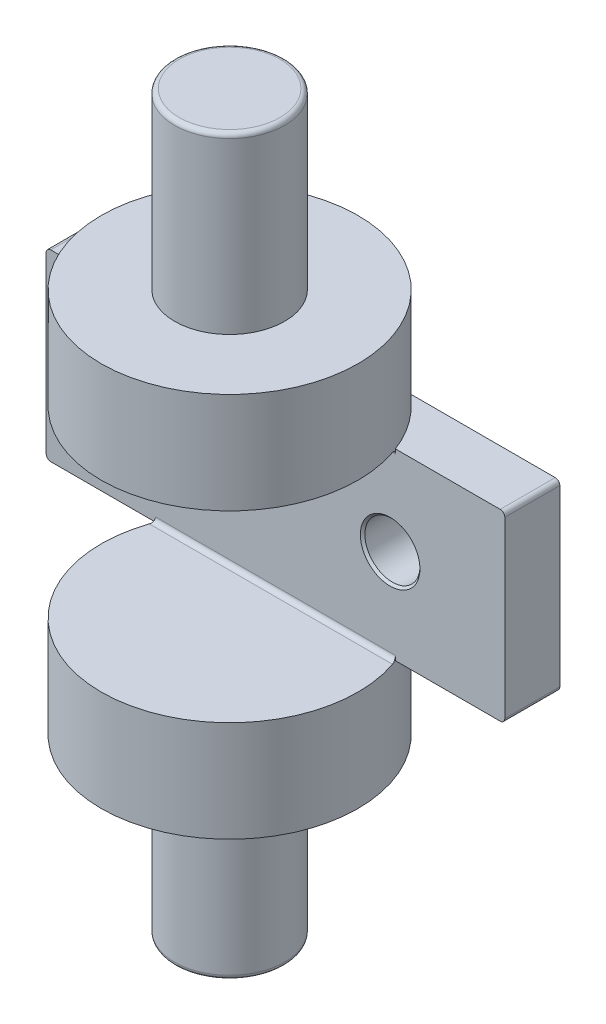
SolidWorks part; units mm, degrees
ref_plane "Alzado" through (0, 0, 0) normal (0, 0, 1) x (1, 0, 0)
ref_plane "Planta" through (0, 0, 0) normal (0, 1, 0) x (1, 0, 0)
ref_plane "Vista lateral" through (0, 0, 0) normal (1, 0, 0) x (0, 0, -1)
sketch "Croquis1" plane through (0, 0, 0) normal (0, 1, 0) x (1, 0, 0)
  circle A0 centre (0, 0) radius 6
  dimension "D1" = 12
extrude "Saliente-Extruir1" add sketch "Croquis1" against normal blind 19
sketch "Croquis2" plane through (0, 0, 0) normal (0, 1, 0) x (1, 0, 0)
  circle A0 centre (0, 0) radius 14
  dimension "D1" = 28
extrude "Saliente-Extruir2" add sketch "Croquis2" along normal blind 11
sketch "Croquis5" plane through (0, 11, 0) normal (0, 1, 0) x (1, 0, 0)
  line L0 (-25, 5) -> (25, 5)
  line L1 (-25, 5) -> (-25, 11)
  line L2 (25, 5) -> (25, 11)
  line L3 (-25, 11) -> (25, 11)
  line L4 (0, 0) -> (0, 14) construction
  point P2 (0, 5)
  dimension "D1" = 5
  dimension "D2" = 50
  dimension "D3" = 6
extrude "Saliente-Extruir6" add sketch "Croquis5" along normal blind 20
sketch "Croquis6" plane through (0, 31, 0) normal (0, 1, 0) x (1, 0, 0)
  circle A0 centre (0, 0) radius 14
extrude "Saliente-Extruir7" add sketch "Croquis6" along normal blind 11
sketch "Croquis7" plane through (0, 42, 0) normal (0, 1, 0) x (1, 0, 0)
  circle A0 centre (0, 0) radius 6
extrude "Saliente-Extruir8" add sketch "Croquis7" along normal blind 19
sketch "Croquis9" plane through (0, 0, -5) normal (0, 0, 1) x (1, 0, 0)
  line L0 (0, 11) -> (0, 31) construction
  line L1 (14, 11) -> (-14, 11) construction
  line L2 (-13.0767, 31) -> (13.0767, 31) construction
  line L3 (-12.5, 21) -> (12.5, 21) construction
  circle A0 centre (-12.5, 21) radius 3
  circle A1 centre (12.5, 21) radius 3
  point P8 (0, 21)
  point P9 (0, 21)
  dimension "D1" = 25
extrude "Cortar-Extruir2" cut sketch "Croquis9" against normal through all both and the other way through all
fillet "Redondeo2" radius 0.5 10 edges at (0, -19, 6) (0, 61, 6) (25, 11, -8) (25, 31, -8) (-25, 11, -8) (-25, 31, -8) (0, 11, -11) (0, 11, -5) (0, 31, -5) (0, 31, -11)
chamfer "Chaflán1" distance 0.25 angle 45 2 edges at (-15.5, 21, -5) (9.5, 21, -5)
